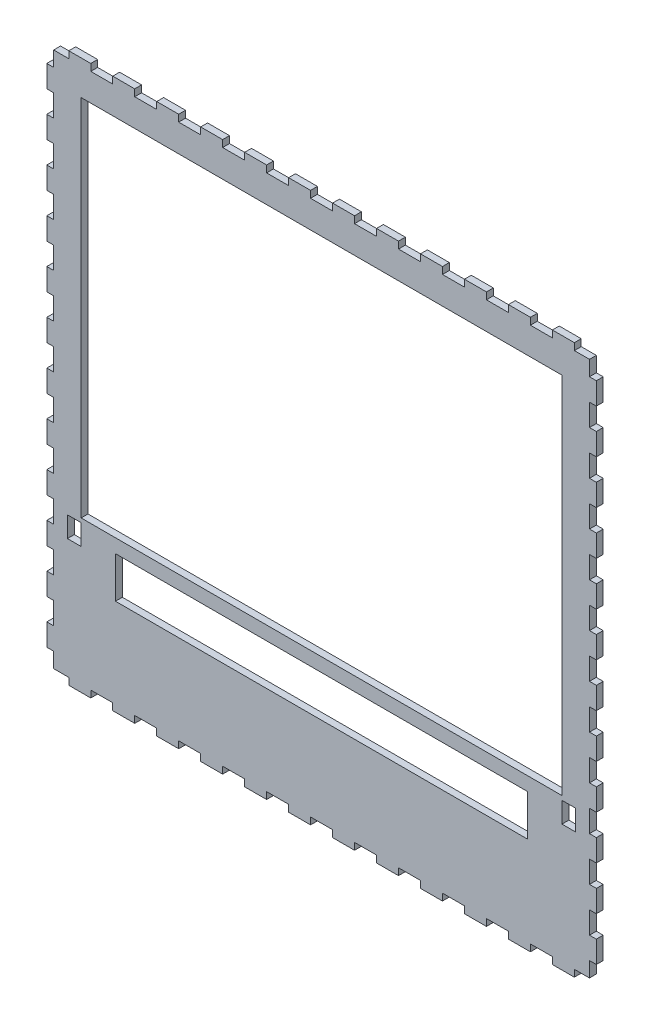
SolidWorks part; units mm, degrees
ref_plane "Plan de face" through (0, 0, 0) normal (0, 0, 1) x (1, 0, 0)
ref_plane "Plan de dessus" through (0, 0, 0) normal (0, 1, 0) x (1, 0, 0)
ref_plane "Plan de droite" through (0, 0, 0) normal (1, 0, 0) x (0, 0, -1)
sketch "Esquisse1" plane through (0, 0, 0) normal (0, 0, 1) x (1, 0, 0)
  line L1 (0, 0) -> (400, 0)
  line L2 (0, 0) -> (0, -400)
  line L3 (0, -400) -> (400, -400)
  line L4 (400, 0) -> (400, -400)
  line L5 (25, -25) -> (375, -25)
  line L6 (25, -25) -> (25, -290)
  line L7 (25, -290) -> (375, -290)
  line L8 (375, -25) -> (375, -290)
  line L9 (50, -300) -> (350, -300)
  line L10 (50, -300) -> (50, -330)
  line L11 (50, -330) -> (350, -330)
  line L12 (350, -300) -> (350, -330)
  dimension "D1" = 400
  dimension "D2" = 400
  dimension "D3" = 25
  dimension "D4" = 25
  dimension "D5" = 25
  dimension "D6" = 110
  dimension "D7" = 30
  dimension "D8" = 10
  dimension "D9" = 300
  dimension "D10" = 25
extrude "Boss.-Extru.1" add sketch "Esquisse1" along normal blind 5
sketch "Esquisse2" plane through (0, 0, 5) normal (0, 0, 1) x (1, 0, 0)
  line L0 (0, -395) -> (0, -400)
  line L3 (0, -395) -> (16, -395)
  line L4 (16, -400) -> (16, -395)
  line L5 (0, -400) -> (16, -400)
  line L8 (0, -400) -> (400, -400) construction
  dimension "D1" = 5
  dimension "D2" = 16
  dimension "D3" = 400
extrude "Enlèv. mat.-Extru.1" cut sketch "Esquisse2" against normal blind 5
pattern_linear "Répétition linéaire1" count 13 spacing 32 along (1, 0, 0) of "Enlèv. mat.-Extru.1"
ref_plane "Plan1" through (0, -200, 0) normal (0, -1, 0) x (-1, 0, 0)
mirror "Symétrie1" about plane through (0, -200, 0) normal (0, -1, 0) of "Répétition linéaire1"
ref_plane "Plan2" through (200, 0, 0) normal (-1, 0, 0) x (0, 0, 1)
sketch "Esquisse3" plane through (0, 0, 5) normal (0, 0, 1) x (1, 0, 0)
  line L0 (19.4538, -400) -> (19.4538, 0) construction
  line L1 (0, -400) -> (5, -400)
  line L2 (0, -400) -> (0, -384)
  line L3 (0, -384) -> (5, -384)
  line L4 (5, -400) -> (5, -384)
  line L5 (16, -400) -> (32, -400) construction
  line L6 (32, 0) -> (16, 0) construction
  line L7 (0, -5) -> (0, -395) construction
  dimension "D2" = 400
  dimension "D1" = 5
  dimension "D3" = 16
extrude "Enlèv. mat.-Extru.2" cut sketch "Esquisse3" against normal blind 10
pattern_linear "Répétition linéaire2" count 13 spacing 32 along (0, 1, 0) of "Enlèv. mat.-Extru.2"
mirror "Symétrie2" about plane through (200, 0, 0) normal (-1, 0, 0) of "Répétition linéaire2"
sketch "Esquisse4" plane through (0, 0, 5) normal (0, 0, 1) x (1, 0, 0)
  line L0 (395, -304) -> (395, -288) construction
  line L1 (385, -293) -> (375, -293)
  line L2 (385, -293) -> (385, -308)
  line L3 (385, -308) -> (375, -308)
  line L4 (375, -293) -> (375, -308)
  line L5 (25, -290) -> (375, -290) construction
  dimension "D1" = 10
  dimension "D2" = 10
  dimension "D3" = 15
  dimension "D4" = 3
extrude "Enlèv. mat.-Extru.3" cut sketch "Esquisse4" against normal blind 5
mirror "Symétrie3" about plane through (200, 0, 0) normal (-1, 0, 0) of "Enlèv. mat.-Extru.3"
equation "\"D5@Esquisse1\"=\"D3@Esquisse1\""
equation "\"D3@Esquisse1\"=\"D4@Esquisse1\""
equation "\"D2@Esquisse2\"=\"D3@Esquisse2\"/25"
equation "\"D3@Esquisse3\"=\"D2@Esquisse3\"/25"
equation "\"D10@Esquisse1\"=(\"D1@Esquisse1\"-2*\"D5@Esquisse1\"-\"D9@Esquisse1\")/2"
